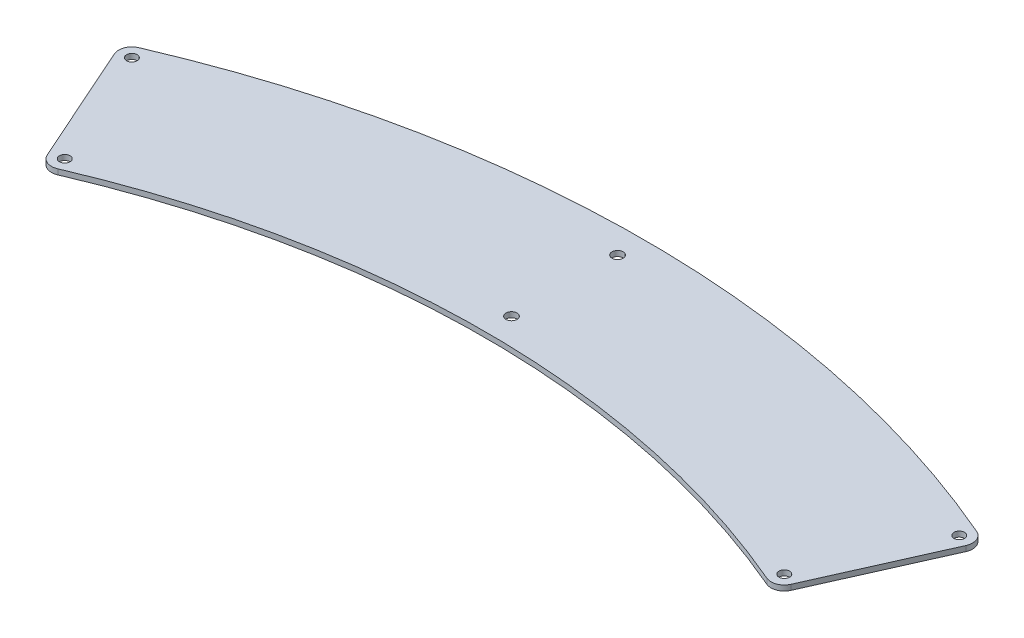
SolidWorks part; units mm, degrees
ref_plane "Спереди" through (0, 0, 0) normal (0, 0, 1) x (1, 0, 0)
ref_plane "Сверху" through (0, 0, 0) normal (0, 1, 0) x (1, 0, 0)
ref_plane "Справа" through (0, 0, 0) normal (1, 0, 0) x (0, 0, -1)
sketch "Эскиз1" plane through (0, 0, 0) normal (0, 1, 0) x (1, 0, 0)
  line L0 (-138.2905, 310.6055) -> (-162.6947, 365.4182) construction
  line L1 (0, 0) -> (0, 259.5027) construction
  line L2 (138.2905, 310.6055) -> (162.6947, 365.4182) construction
  line L3 (-138.2905, 310.6055) -> (-162.6947, 365.4182)
  line L4 (162.6947, 365.4182) -> (138.2905, 310.6055)
  line L10 (0, 344.4859) -> (0, 245.0378) construction
  line L11 (0, 0) -> (-162.6947, 365.4182) construction
  line L12 (0, 0) -> (162.6947, 365.4182) construction
  arc A0 (162.6947, 365.4182) -> (-162.6947, 365.4182) centre (0, 0) ccw construction
  arc A1 (162.6947, 365.4182) -> (-162.6947, 365.4182) centre (0, 0) ccw
  arc A2 (138.2905, 310.6055) -> (-138.2905, 310.6055) centre (0, 0) ccw
  dimension "D1" = 340
  dimension "D2" = 400
  dimension "D4" = 24
  dimension "D5" = 24
sheet metal parameters "Листовой металл1" thickness 2 parameters "D1"=1.2, "Толщина"=2
base flange "Базовая кромка1" sketch "Эскиз1" thickness 2 reverse thickness direction no parameters "D1"=1.2
fillet "Скругление1" radius 5 4 edges at (162.6947, -1, -365.4182) (138.2905, -1, -310.6055) (-162.6947, -1, -365.4182) (-138.2905, -1, -310.6055)
sketch "Эскиз2" plane through (0, 0, 0) normal (0, 1, 0) x (1, 0, 0)
  circle A0 centre (0, 350) radius 2.1
  circle A1 centre (0, 390) radius 2.1
extrude "Вырез-Вытянуть1" cut sketch "Эскиз2" against normal blind 10 normal cut yes
sketch "Эскиз3" plane through (0, 0, 0) normal (0, 1, 0) x (1, 0, 0)
  circle A0 centre (-135.7417, 317.1738) radius 2
  circle A1 centre (-156.0804, 362.8552) radius 2
  circle A2 centre (135.7417, 317.1738) radius 2
  circle A3 centre (156.0804, 362.8552) radius 2
  dimension "D1" = 4
  dimension "D2" = 4
  dimension "D3" = 4
  dimension "D4" = 4
extrude "Вырез-Вытянуть2" cut sketch "Эскиз3" against normal blind 10 normal cut yes
flat pattern "Развертка1" [suppressed]
sketch "Сгиб-Линии1" plane through (0, 0, 0) normal (0, 1, 0) x (1, 0, 0)
sketch3d "Граничная рамка1" [suppressed]
  line L0 (-105.7369, 160.0484, 0) -> (154.0999, 114.2321, 0) construction
  line L1 (-89.9793, 249.4139, 0) -> (169.8575, 203.5977, 0) construction
  line L2 (-105.7369, 160.0484, 0) -> (-89.9793, 249.4139, 0) construction
  line L3 (154.0999, 114.2321, 0) -> (169.8575, 203.5977, 0) construction
